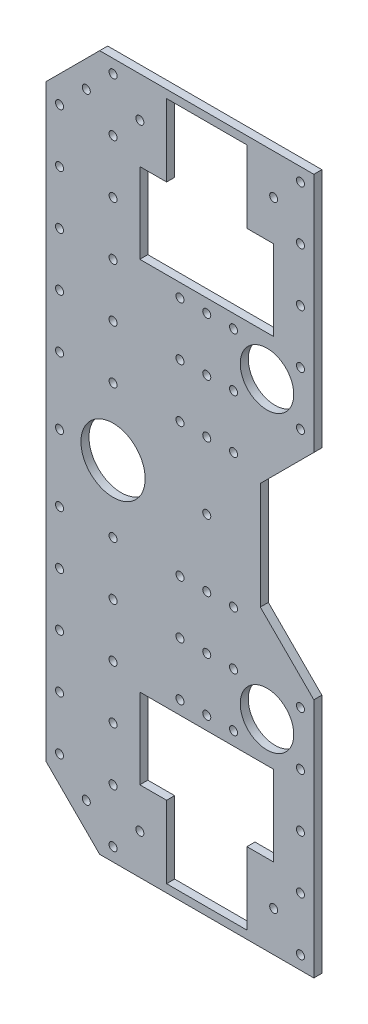
SolidWorks part; units mm, degrees
ref_plane "Front Plane" through (0, 0, 0) normal (0, 0, 1) x (1, 0, 0)
ref_plane "Top Plane" through (0, 0, 0) normal (0, 1, 0) x (1, 0, 0)
ref_plane "Right Plane" through (0, 0, 0) normal (1, 0, 0) x (0, 0, -1)
ref_axis "Axis1" through (-88.99, 0, 0) along (1, 0, 0)
ref_axis "Axis3" through (0, -55, 0) along (0, 1, 0)
sketch "Sketch1" plane through (0, 0, 0) normal (0, 0, 1) x (1, 0, 0)
  line L0 (-60, 110) -> (-60, -110)
  line L1 (-60, -110) -> (-40, -130)
  line L2 (-40, -130) -> (40, -130)
  line L3 (40, -130) -> (40, -40)
  line L4 (40, -40) -> (20, -20)
  line L5 (20, -20) -> (20, 20)
  line L6 (20, 20) -> (40, 40)
  line L7 (40, 40) -> (40, 130)
  line L8 (40, 130) -> (-40, 130)
  line L9 (-40, 130) -> (-60, 110)
  line L10 (-88.99, 0) -> (88.99, 0) construction
  line L12 (0, -55) -> (0, 55) construction
  point P2 (-60, 0)
  point P14 (-41.3479, 0)
  dimension "D1" = 220
  dimension "D2" = 80
  dimension "D3" = 20
  dimension "D4" = 20
  dimension "D5" = 90
  dimension "D6" = 60
  dimension "D7" = 20
  dimension "D8" = 40
extrude "Main" add sketch "Sketch1" along normal blind 3
sketch "Sketch2" plane through (0, 0, 3) normal (0, 0, 1) x (1, 0, 0)
  line L0 (-25, 100) -> (-25, 70)
  line L1 (-25, 70) -> (25, 70)
  line L2 (25, 70) -> (25, 100)
  line L3 (25, 100) -> (15, 100)
  line L4 (15, 100) -> (15, 127)
  line L5 (15, 127) -> (-15, 127)
  line L6 (-15, 127) -> (-15, 100)
  line L7 (-15, 100) -> (-25, 100)
  line L8 (0, -55) -> (0, 55) construction
  line L9 (-88.99, 0) -> (88.99, 0) construction
  point P8 (0, 70)
  dimension "D1" = 50
  dimension "D2" = 70
  dimension "D3" = 30
  dimension "D4" = 27
  dimension "D5" = 30
extrude "MotorCoderLeftHole" cut sketch "Sketch2" against normal through all
sketch "Sketch4" plane through (0, 0, 3) normal (0, 0, 1) x (1, 0, 0)
  circle A0 centre (-55, 105) radius 1.5
  point P5 (-59.8016, 110.1984)
  dimension "D1" = 3
  dimension "D2" = 5
  dimension "D3" = 5
extrude "BottomLeftHole" cut sketch "Sketch4" against normal through all
pattern_linear "BottomLeftHoleLPattern" count 5 spacing 20 along (0, -1, 0) of "BottomLeftHole"
sketch "Sketch5" plane through (0, 0, 3) normal (0, 0, 1) x (1, 0, 0)
  circle A0 centre (-35, 125) radius 1.5
  point P2 (-42.4105, 122.5304)
  point P4 (-33.4878, 125)
  dimension "D3" = 3
  dimension "D1" = 5
  dimension "D2" = 5
extrude "BottomLeftHole2" cut sketch "Sketch5" against normal through all
pattern_linear "BottomLeftHole2LPattern" count 6 spacing 20 along (0, -1, 0) of "BottomLeftHole2"
sketch "Sketch6" plane through (0, 0, 3) normal (0, 0, 1) x (1, 0, 0)
  line L0 (40, 40) -> (40, 130) construction
  line L1 (40, 130) -> (-40, 130) construction
  circle A0 centre (35, 125) radius 1.5
  dimension "D1" = 3
  dimension "D2" = 5
  dimension "D3" = 5
extrude "TopLeftHole" cut sketch "Sketch6" against normal through all
pattern_linear "TopLeftHoleLPattern" count 5 spacing 20 along (0, -1, 0) of "TopLeftHole"
sketch "Sketch7" plane through (0, 0, 3) normal (0, 0, 1) x (1, 0, 0)
  line L0 (-88.99, 0) -> (88.99, 0) construction
  line L1 (0, -55) -> (0, 55) construction
  circle A0 centre (0, 65) radius 1.5
  circle A1 centre (-10, 65) radius 1.5
  circle A2 centre (10, 65) radius 1.5
  point P4 (0, 0)
  dimension "D1" = 3
  dimension "D2" = 65
  dimension "D3" = 10
  dimension "D4" = 10
extrude "MotorFixHoles" cut sketch "Sketch7" against normal through all
pattern_linear "MotorFixHoleLPattern" count 3 spacing 20 along (0, -1, 0) of "MotorFixHoles"
sketch "Sketch8" plane through (0, 0, 3) normal (0, 0, 1) x (1, 0, 0)
  line L0 (40, 130) -> (-40, 130) construction
  circle A0 centre (-45, 115) radius 1.5
  circle A1 centre (-25, 115) radius 1.5
  circle A2 centre (25, 115) radius 1.5
  circle A3 centre (-55, 105) radius 1.5 construction
  circle A4 centre (35, 125) radius 1.5 construction
  point P10 (0, 0)
  point P13 (25.1614, 111.7129)
  point P14 (0, 0)
  dimension "D1" = 10
  dimension "D3" = 3
  dimension "D5" = 10
  dimension "D2" = 15
  dimension "D4" = 20
extrude "CoderHole" cut sketch "Sketch8" against normal through all
mirror "Mirror1" about plane through (0, 0, 0) normal (0, 1, 0) of "CoderHole", "TopLeftHoleLPattern", "BottomLeftHoleLPattern", "MotorCoderLeftHole", "BottomLeftHole2LPattern", "MotorFixHoleLPattern"
sketch "Sketch3" plane through (0, 0, 3) normal (0, 0, 1) x (1, 0, 0)
  line L0 (-88.99, 0) -> (88.99, 0) construction
  line L1 (-60, 110) -> (-60, -110) construction
  line L3 (0, -55) -> (0, 55) construction
  line L4 (22.5, 55) -> (22.5, -55) construction
  circle A0 centre (-35, 0) radius 12
  circle A1 centre (22.5, 55) radius 10
  circle A2 centre (22.5, -55) radius 10
  circle A3 centre (0, 0) radius 1.5
  circle A4 centre (-55, 0) radius 1.5
  point P10 (22.5, 0)
  dimension "D1" = 24
  dimension "D3" = 20
  dimension "D6" = 3
  dimension "D2" = 25
  dimension "D4" = 55
  dimension "D5" = 22.5
  dimension "D7" = 5
extrude "BigHoles" cut sketch "Sketch3" against normal through all
